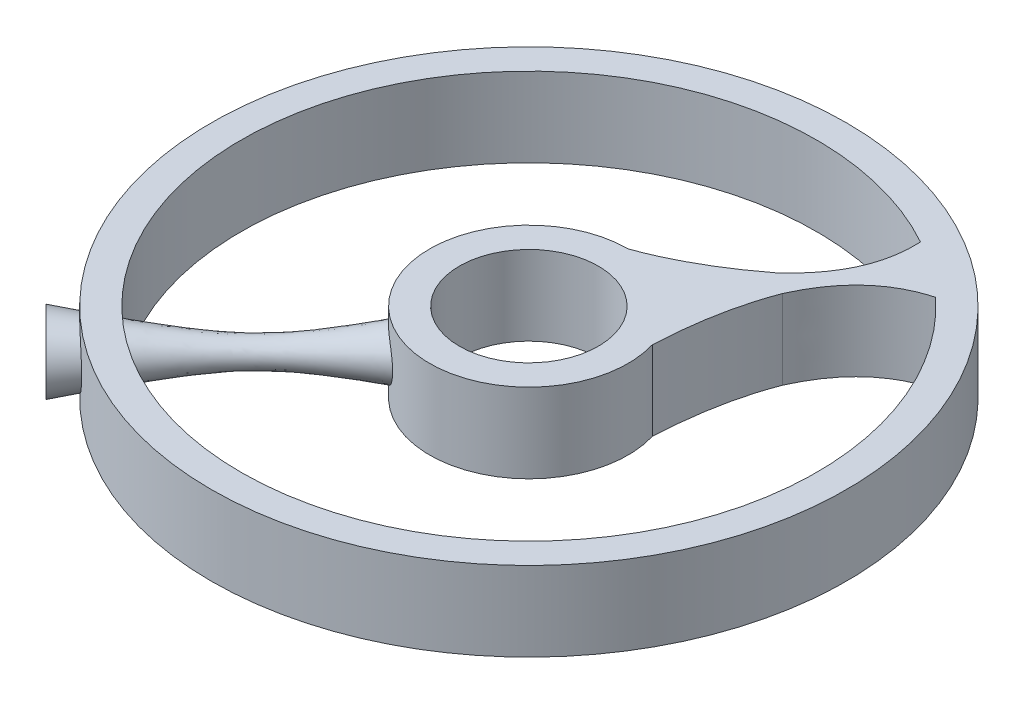
SolidWorks part; units mm, degrees
ref_plane "Front Plane" through (0, 0, 0) normal (0, 0, 1) x (1, 0, 0)
ref_plane "Top Plane" through (0, 0, 0) normal (0, 1, 0) x (1, 0, 0)
ref_plane "Right Plane" through (0, 0, 0) normal (1, 0, 0) x (0, 0, -1)
sketch "Sketch2" plane through (0, 0, 0) normal (0, 1, 0) x (1, 0, 0)
  circle A0 centre (0, 0) radius 160
  circle A1 centre (0, 0) radius 145
extrude "Outer Ring" add sketch "Sketch2" along normal blind 40
sketch "Sketch3" plane through (0, 0, 0) normal (0, 1, 0) x (1, 0, 0)
  circle A0 centre (0, 0) radius 50
  circle A1 centre (0, 0) radius 35
extrude "Inner" add sketch "Sketch3" along normal blind 40 separate body
sketch "Sketch4" plane through (0, 0, 0) normal (0, 1, 0) x (1, 0, 0)
  line L0 (0, 0) -> (85.2289, 117.3075) construction
  line L1 (0, 0) -> (145, 0) construction
  line L2 (0, 0) -> (0, 145) construction
  line L3 (0, 50) -> (70.6402, 120.7117) construction
  line L4 (47.9169, 14.2819) -> (92.9746, 104.4848) construction
  line L5 (35.3201, 85.3559) -> (70.4458, 59.3834) construction
  arc A0 (0, 50) -> (47.9169, 14.2819) centre (0, 0) cw
  circle A1 centre (0, 0) radius 145 construction
  arc A2 (70.6402, 126.6292) -> (98.6025, 106.3134) centre (0, 0) cw
  circle A3 centre (0, 0) radius 50 construction
  spline S0 degree 3 poles (0, 50) (15.5027, 55.3917) (32.3208, 64.9165) (47.9169, 76.9392) knots 0 0 0 0 0.490217 0.490217 0.490217 0.490217
  spline S1 degree 3 poles (47.9169, 14.2819) (48.6558, 30.6788) (51.2995, 50.9667) (58.3664, 69.3472) knots 0 0 0 0 0.490217 0.490217 0.490217 0.490217
  spline S2 degree 2 poles (47.9169, 76.9392) (72.0035, 98.6781) (70.6402, 126.6292) knots 0 0 0 1 1 1
  spline S3 degree 2 poles (58.3664, 69.3472) (71.5982, 98.9726) (98.6025, 106.3134) knots 0 0 0 1 1 1
  dimension "D1" = 145
extrude "Strut [Extruded Form]" add sketch "Sketch4" along normal blind 40
ref_plane "Plane1" through (0, 20, 0) normal (0, 1, 0) x (1, 0, 0)
sketch "Sketch8" plane through (0, 20, 0) normal (0, 1, 0) x (1, 0, 0)
  line L0 (0, 0) -> (0, 145) construction
  line L1 (0, 0) -> (-145, 0) construction
  line L2 (0, 0) -> (-85.2289, 117.3075) construction
  line L3 (-85.2289, 117.3075) -> (0, 0)
  arc A0 (70.6402, 126.6292) -> (98.6025, 106.3134) centre (0, 0) ccw construction
ref_plane "Plane2" through (0, 0, 0) normal (-0.7071, 0, 0.7071) x (0.7071, 0, 0.7071)
ref_plane "Plane3" through (-30.4056, 0, 30.4056) normal (-0.7071, 0, 0.7071) x (0.7071, 0, 0.7071)
ref_plane "Plane4" through (-60.8112, 0, 60.8112) normal (-0.7071, 0, 0.7071) x (0.7071, 0, 0.7071)
ref_plane "Plane5" through (-91.2168, 0, 91.2168) normal (-0.7071, 0, 0.7071) x (0.7071, 0, 0.7071)
ref_plane "Plane6" through (-121.6224, 0, 121.6224) normal (-0.7071, 0, 0.7071) x (0.7071, 0, 0.7071)
sketch "Sketch10" plane through (0, 0, 0) normal (-0.7071, 0, 0.7071) x (0.7071, 0, 0.7071)
  line L0 (176, 20) -> (-176, 20) construction
  circle A0 centre (0, 20) radius 13
sketch "Sketch11" plane through (-30.4056, 0, 30.4056) normal (-0.7071, 0, 0.7071) x (0.7071, 0, 0.7071)
  circle A0 centre (0, 20) radius 13
sketch "Sketch12" plane through (-60.8112, 0, 60.8112) normal (-0.7071, 0, 0.7071) x (0.7071, 0, 0.7071)
  circle A0 centre (0, 20) radius 7
sketch "Sketch14" plane through (-121.6224, 0, 121.6224) normal (-0.7071, 0, 0.7071) x (0.7071, 0, 0.7071)
  circle A0 centre (0, 20.0857) radius 17
loft "Loft1" add profiles "Sketch14", "Sketch11" connector at (-133.6266, 20.9772, 109.6181) connector at (-24.7578, 30.257, 36.0534)
